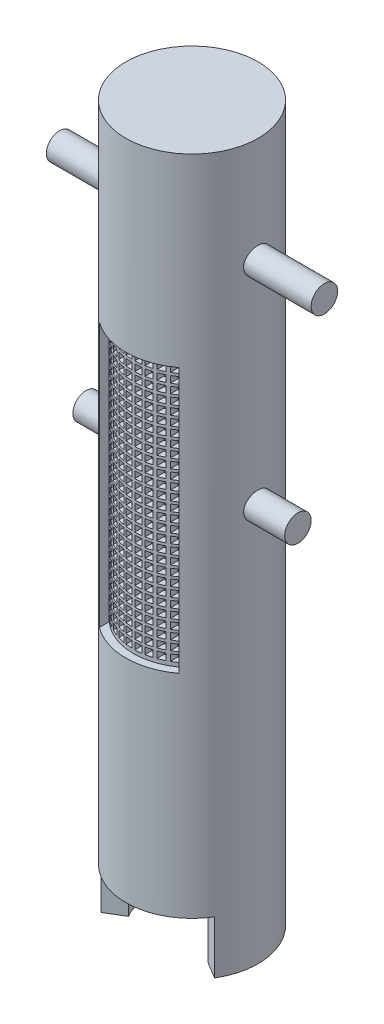
SolidWorks part; units mm, degrees
ref_plane "Front Plane" through (0, 0, 0) normal (0, 0, 1) x (1, 0, 0)
ref_plane "Top Plane" through (0, 0, 0) normal (0, 1, 0) x (1, 0, 0)
ref_plane "Right Plane" through (0, 0, 0) normal (1, 0, 0) x (0, 0, -1)
sketch "Sketch2" plane through (0, 0, 0) normal (0, 1, 0) x (1, 0, 0)
  circle A0 centre (0, 0) radius 5
  circle A1 centre (0, 0) radius 3.5
  dimension "D1" = 10
  dimension "D2" = 7
extrude "Boss-Extrude1" add sketch "Sketch2" along normal blind 40
sketch "Sketch3" plane through (0, 40, 0) normal (0, 1, 0) x (1, 0, 0)
  circle A0 centre (0, 0) radius 5
  circle A1 centre (0, 0) radius 1
  dimension "D1" = 10
  dimension "D2" = 2
sketch "Sketch4" plane through (0, 40, 0) normal (0, 1, 0) x (1, 0, 0)
  line L0 (3, 0) -> (3, -5)
  line L1 (3, 0) -> (-3, 0)
  line L3 (3, -5) -> (-3, -5)
  line L4 (-3, 0) -> (-3, -5)
  dimension "D1" = 6
  dimension "D2" = 5
  dimension "D3" = 3
  dimension "D4" = 5
  dimension "D5" = 3
extrude "Cut-Extrude1" cut sketch "Sketch4" against normal blind 20
extrude "Boss-Extrude2" add sketch "Sketch3" along normal blind 1
sketch "Sketch5" plane through (0, 41, 0) normal (0, 1, 0) x (1, 0, 0)
  circle A0 centre (0, 0) radius 5
  circle A1 centre (0, 0) radius 3.5
  dimension "D1" = 10
  dimension "D2" = 7
extrude "Boss-Extrude3" add sketch "Sketch5" along normal blind 10
sketch "Sketch6" plane through (0, 51, 0) normal (0, 1, 0) x (1, 0, 0)
  line L0 (2.5, 0) -> (2.5, 5)
  line L5 (2.5, 0) -> (-2.5, 0)
  line L7 (2.5, 5) -> (-2.5, 5)
  line L8 (-2.5, 0) -> (-2.5, 5)
  line L9 (-5.5, 0) -> (5.5, 0) construction
  line L10 (0, -5.5) -> (0, 5.5) construction
  dimension "D1" = 5
  dimension "D2" = 5
  dimension "D3" = 5
  dimension "D4" = 2.5
extrude "Cut-Extrude2" cut sketch "Sketch6" against normal blind 6
sketch "Sketch7" plane through (0, 51, 0) normal (0, 1, 0) x (1, 0, 0)
  circle A0 centre (0, 0) radius 5
  dimension "D1" = 10
extrude "Boss-Extrude4" add sketch "Sketch7" along normal blind 3
sketch "Sketch9" plane through (0, 20, 0) normal (0, 1, 0) x (1, 0, 0)
  line L0 (-3, -1.8028) -> (-3, -4) construction
  line L1 (3, -1.8028) -> (3, -4) construction
  line L2 (-3, -1.8028) -> (-3, -4) construction
  line L3 (3, -2.5286) -> (3, -3.2507)
  line L4 (-3, -2.5286) -> (-3, -3.2507)
  arc A0 (-3, -1.8028) -> (3, -1.8028) centre (0, 0) ccw construction
  arc A1 (-3, -2.9014) -> (3, -2.9014) centre (0, 0) ccw construction
  arc A2 (-3, -3.2507) -> (3.1797, -3.0752) centre (0, 0) ccw construction
  arc A3 (-3, -2.5286) -> (3, -2.5286) centre (0, 0) ccw
  arc A4 (-2.8203, -2.7276) -> (2.8203, -2.7276) centre (0, 0) ccw construction
  arc A5 (-3.1797, -3.0752) -> (3.1797, -3.0752) centre (0, 0) ccw construction
  arc A6 (-3, -3.2507) -> (3, -3.2507) centre (0, 0) ccw
  dimension "D1" = 0.25
  dimension "D2" = 0.25
extrude "Boss-Extrude5" add sketch "Sketch9" along normal up to surface (20 mm away) up to face at (0, 40, 1.8257)
ref_plane "Plane1" through (0, 0, 4.4235) normal (0, 0, 1) x (1, 0, 0)
sketch "Sketch10" plane through (0, 0, 4.4235) normal (0, 0, 1) x (1, 0, 0)
  line L0 (-3, 20) -> (3, 20) construction
  line L1 (3, 20) -> (3, 40) construction
  line L2 (3, 40) -> (-3, 40) construction
  line L3 (-3, 40) -> (-3, 20) construction
  line L4 (-2, 20.3) -> (-2, 20.8)
  line L5 (-2.7, 20.3) -> (-2.2, 20.3)
  line L6 (-2.7, 20.3) -> (-2.7, 20.8)
  line L7 (-2.7, 20.8) -> (-2.2, 20.8)
  line L8 (-2.2, 20.3) -> (-2.2, 20.8)
  line L9 (-2, 20.3) -> (-1.5, 20.3)
  line L10 (-1.5, 20.3) -> (-1.5, 20.8)
  line L11 (-2, 20.8) -> (-1.5, 20.8)
  line L12 (-1.3, 20.3) -> (-1.3, 20.8)
  line L13 (-1.3, 20.3) -> (-0.8, 20.3)
  line L14 (-0.8, 20.3) -> (-0.8, 20.8)
  line L15 (-1.3, 20.8) -> (-0.8, 20.8)
  line L16 (-0.6, 20.3) -> (-0.6, 20.8)
  line L17 (-0.6, 20.3) -> (-0.1, 20.3)
  line L18 (-0.1, 20.3) -> (-0.1, 20.8)
  line L19 (-0.6, 20.8) -> (-0.1, 20.8)
  line L20 (0.1, 20.3) -> (0.1, 20.8)
  line L21 (0.1, 20.3) -> (0.6, 20.3)
  line L22 (0.6, 20.3) -> (0.6, 20.8)
  line L23 (0.1, 20.8) -> (0.6, 20.8)
  line L24 (0.8, 20.3) -> (0.8, 20.8)
  line L25 (0.8, 20.3) -> (1.3, 20.3)
  line L26 (1.3, 20.3) -> (1.3, 20.8)
  line L27 (0.8, 20.8) -> (1.3, 20.8)
  line L28 (1.5, 20.3) -> (1.5, 20.8)
  line L29 (1.5, 20.3) -> (2, 20.3)
  line L30 (2, 20.3) -> (2, 20.8)
  line L31 (1.5, 20.8) -> (2, 20.8)
  line L32 (2.2, 20.3) -> (2.2, 20.8)
  line L33 (2.2, 20.3) -> (2.7, 20.3)
  line L34 (2.7, 20.3) -> (2.7, 20.8)
  line L35 (2.2, 20.8) -> (2.7, 20.8)
  line L36 (-2.7, 21) -> (-2.7, 21.5)
  line L37 (-2.7, 21) -> (-2.2, 21)
  line L38 (-2.2, 21) -> (-2.2, 21.5)
  line L39 (-2.7, 21.5) -> (-2.2, 21.5)
  line L40 (-2, 21) -> (-2, 21.5)
  line L41 (-2, 21.5) -> (-1.5, 21.5)
  line L42 (-1.5, 21) -> (-1.5, 21.5)
  line L43 (-2, 21) -> (-1.5, 21)
  line L44 (-1.3, 21) -> (-1.3, 21.5)
  line L45 (-1.3, 21.5) -> (-0.8, 21.5)
  line L46 (-0.8, 21) -> (-0.8, 21.5)
  line L47 (-1.3, 21) -> (-0.8, 21)
  line L48 (-0.6, 21) -> (-0.6, 21.5)
  line L49 (-0.6, 21.5) -> (-0.1, 21.5)
  line L50 (-0.1, 21) -> (-0.1, 21.5)
  line L51 (-0.6, 21) -> (-0.1, 21)
  line L52 (0.1, 21) -> (0.1, 21.5)
  line L53 (0.1, 21.5) -> (0.6, 21.5)
  line L54 (0.6, 21) -> (0.6, 21.5)
  line L55 (0.1, 21) -> (0.6, 21)
  line L56 (0.8, 21) -> (0.8, 21.5)
  line L57 (0.8, 21.5) -> (1.3, 21.5)
  line L58 (1.3, 21) -> (1.3, 21.5)
  line L59 (0.8, 21) -> (1.3, 21)
  line L60 (1.5, 21) -> (1.5, 21.5)
  line L61 (1.5, 21.5) -> (2, 21.5)
  line L62 (2, 21) -> (2, 21.5)
  line L63 (1.5, 21) -> (2, 21)
  line L64 (2.2, 21) -> (2.2, 21.5)
  line L65 (2.2, 21.5) -> (2.7, 21.5)
  line L66 (2.7, 21) -> (2.7, 21.5)
  line L67 (2.2, 21) -> (2.7, 21)
  line L68 (-2.7, 21.7) -> (-2.7, 22.2)
  line L69 (-2.7, 21.7) -> (-2.2, 21.7)
  line L70 (-2.2, 21.7) -> (-2.2, 22.2)
  line L71 (-2.7, 22.2) -> (-2.2, 22.2)
  line L72 (-2, 21.7) -> (-2, 22.2)
  line L73 (-2, 22.2) -> (-1.5, 22.2)
  line L74 (-1.5, 21.7) -> (-1.5, 22.2)
  line L75 (-2, 21.7) -> (-1.5, 21.7)
  line L76 (-1.3, 21.7) -> (-1.3, 22.2)
  line L77 (-1.3, 22.2) -> (-0.8, 22.2)
  line L78 (-0.8, 21.7) -> (-0.8, 22.2)
  line L79 (-1.3, 21.7) -> (-0.8, 21.7)
  line L80 (-0.6, 21.7) -> (-0.6, 22.2)
  line L81 (-0.6, 22.2) -> (-0.1, 22.2)
  line L82 (-0.1, 21.7) -> (-0.1, 22.2)
  line L83 (-0.6, 21.7) -> (-0.1, 21.7)
  line L84 (0.1, 21.7) -> (0.1, 22.2)
  line L85 (0.1, 22.2) -> (0.6, 22.2)
  line L86 (0.6, 21.7) -> (0.6, 22.2)
  line L87 (0.1, 21.7) -> (0.6, 21.7)
  line L88 (0.8, 21.7) -> (0.8, 22.2)
  line L89 (0.8, 22.2) -> (1.3, 22.2)
  line L90 (1.3, 21.7) -> (1.3, 22.2)
  line L91 (0.8, 21.7) -> (1.3, 21.7)
  line L92 (1.5, 21.7) -> (1.5, 22.2)
  line L93 (1.5, 22.2) -> (2, 22.2)
  line L94 (2, 21.7) -> (2, 22.2)
  line L95 (1.5, 21.7) -> (2, 21.7)
  line L96 (2.2, 21.7) -> (2.2, 22.2)
  line L97 (2.2, 22.2) -> (2.7, 22.2)
  line L98 (2.7, 21.7) -> (2.7, 22.2)
  line L99 (2.2, 21.7) -> (2.7, 21.7)
  line L100 (-2.7, 22.4) -> (-2.7, 22.9)
  line L101 (-2.7, 22.4) -> (-2.2, 22.4)
  line L102 (-2.2, 22.4) -> (-2.2, 22.9)
  line L103 (-2.7, 22.9) -> (-2.2, 22.9)
  line L104 (-2, 22.4) -> (-2, 22.9)
  line L105 (-2, 22.9) -> (-1.5, 22.9)
  line L106 (-1.5, 22.4) -> (-1.5, 22.9)
  line L107 (-2, 22.4) -> (-1.5, 22.4)
  line L108 (-1.3, 22.4) -> (-1.3, 22.9)
  line L109 (-1.3, 22.9) -> (-0.8, 22.9)
  line L110 (-0.8, 22.4) -> (-0.8, 22.9)
  line L111 (-1.3, 22.4) -> (-0.8, 22.4)
  line L112 (-0.6, 22.4) -> (-0.6, 22.9)
  line L113 (-0.6, 22.9) -> (-0.1, 22.9)
  line L114 (-0.1, 22.4) -> (-0.1, 22.9)
  line L115 (-0.6, 22.4) -> (-0.1, 22.4)
  line L116 (0.1, 22.4) -> (0.1, 22.9)
  line L117 (0.1, 22.9) -> (0.6, 22.9)
  line L118 (0.6, 22.4) -> (0.6, 22.9)
  line L119 (0.1, 22.4) -> (0.6, 22.4)
  line L120 (0.8, 22.4) -> (0.8, 22.9)
  line L121 (0.8, 22.9) -> (1.3, 22.9)
  line L122 (1.3, 22.4) -> (1.3, 22.9)
  line L123 (0.8, 22.4) -> (1.3, 22.4)
  line L124 (1.5, 22.4) -> (1.5, 22.9)
  line L125 (1.5, 22.9) -> (2, 22.9)
  line L126 (2, 22.4) -> (2, 22.9)
  line L127 (1.5, 22.4) -> (2, 22.4)
  line L128 (2.2, 22.4) -> (2.2, 22.9)
  line L129 (2.2, 22.9) -> (2.7, 22.9)
  line L130 (2.7, 22.4) -> (2.7, 22.9)
  line L131 (2.2, 22.4) -> (2.7, 22.4)
  line L132 (-2.7, 23.1) -> (-2.7, 23.6)
  line L133 (-2.7, 23.1) -> (-2.2, 23.1)
  line L134 (-2.2, 23.1) -> (-2.2, 23.6)
  line L135 (-2.7, 23.6) -> (-2.2, 23.6)
  line L136 (-2, 23.1) -> (-2, 23.6)
  line L137 (-2, 23.6) -> (-1.5, 23.6)
  line L138 (-1.5, 23.1) -> (-1.5, 23.6)
  line L139 (-2, 23.1) -> (-1.5, 23.1)
  line L140 (-1.3, 23.1) -> (-1.3, 23.6)
  line L141 (-1.3, 23.6) -> (-0.8, 23.6)
  line L142 (-0.8, 23.1) -> (-0.8, 23.6)
  line L143 (-1.3, 23.1) -> (-0.8, 23.1)
  line L144 (-0.6, 23.1) -> (-0.6, 23.6)
  line L145 (-0.6, 23.6) -> (-0.1, 23.6)
  line L146 (-0.1, 23.1) -> (-0.1, 23.6)
  line L147 (-0.6, 23.1) -> (-0.1, 23.1)
  line L148 (0.1, 23.1) -> (0.1, 23.6)
  line L149 (0.1, 23.6) -> (0.6, 23.6)
  line L150 (0.6, 23.1) -> (0.6, 23.6)
  line L151 (0.1, 23.1) -> (0.6, 23.1)
  line L152 (0.8, 23.1) -> (0.8, 23.6)
  line L153 (0.8, 23.6) -> (1.3, 23.6)
  line L154 (1.3, 23.1) -> (1.3, 23.6)
  line L155 (0.8, 23.1) -> (1.3, 23.1)
  line L156 (1.5, 23.1) -> (1.5, 23.6)
  line L157 (1.5, 23.6) -> (2, 23.6)
  line L158 (2, 23.1) -> (2, 23.6)
  line L159 (1.5, 23.1) -> (2, 23.1)
  line L160 (2.2, 23.1) -> (2.2, 23.6)
  line L161 (2.2, 23.6) -> (2.7, 23.6)
  line L162 (2.7, 23.1) -> (2.7, 23.6)
  line L163 (2.2, 23.1) -> (2.7, 23.1)
  line L164 (-2.7, 23.8) -> (-2.7, 24.3)
  line L165 (-2.7, 23.8) -> (-2.2, 23.8)
  line L166 (-2.2, 23.8) -> (-2.2, 24.3)
  line L167 (-2.7, 24.3) -> (-2.2, 24.3)
  line L168 (-2, 23.8) -> (-2, 24.3)
  line L169 (-2, 24.3) -> (-1.5, 24.3)
  line L170 (-1.5, 23.8) -> (-1.5, 24.3)
  line L171 (-2, 23.8) -> (-1.5, 23.8)
  line L172 (-1.3, 23.8) -> (-1.3, 24.3)
  line L173 (-1.3, 24.3) -> (-0.8, 24.3)
  line L174 (-0.8, 23.8) -> (-0.8, 24.3)
  line L175 (-1.3, 23.8) -> (-0.8, 23.8)
  line L176 (-0.6, 23.8) -> (-0.6, 24.3)
  line L177 (-0.6, 24.3) -> (-0.1, 24.3)
  line L178 (-0.1, 23.8) -> (-0.1, 24.3)
  line L179 (-0.6, 23.8) -> (-0.1, 23.8)
  line L180 (0.1, 23.8) -> (0.1, 24.3)
  line L181 (0.1, 24.3) -> (0.6, 24.3)
  line L182 (0.6, 23.8) -> (0.6, 24.3)
  line L183 (0.1, 23.8) -> (0.6, 23.8)
  line L184 (0.8, 23.8) -> (0.8, 24.3)
  line L185 (0.8, 24.3) -> (1.3, 24.3)
  line L186 (1.3, 23.8) -> (1.3, 24.3)
  line L187 (0.8, 23.8) -> (1.3, 23.8)
  line L188 (1.5, 23.8) -> (1.5, 24.3)
  line L189 (1.5, 24.3) -> (2, 24.3)
  line L190 (2, 23.8) -> (2, 24.3)
  line L191 (1.5, 23.8) -> (2, 23.8)
  line L192 (2.2, 23.8) -> (2.2, 24.3)
  line L193 (2.2, 24.3) -> (2.7, 24.3)
  line L194 (2.7, 23.8) -> (2.7, 24.3)
  line L195 (2.2, 23.8) -> (2.7, 23.8)
  line L196 (-2.7, 24.5) -> (-2.7, 25)
  line L197 (-2.7, 24.5) -> (-2.2, 24.5)
  line L198 (-2.2, 24.5) -> (-2.2, 25)
  line L199 (-2.7, 25) -> (-2.2, 25)
  line L200 (-2, 24.5) -> (-2, 25)
  line L201 (-2, 25) -> (-1.5, 25)
  line L202 (-1.5, 24.5) -> (-1.5, 25)
  line L203 (-2, 24.5) -> (-1.5, 24.5)
  line L204 (-1.3, 24.5) -> (-1.3, 25)
  line L205 (-1.3, 25) -> (-0.8, 25)
  line L206 (-0.8, 24.5) -> (-0.8, 25)
  line L207 (-1.3, 24.5) -> (-0.8, 24.5)
  line L208 (-0.6, 24.5) -> (-0.6, 25)
  line L209 (-0.6, 25) -> (-0.1, 25)
  line L210 (-0.1, 24.5) -> (-0.1, 25)
  line L211 (-0.6, 24.5) -> (-0.1, 24.5)
  line L212 (0.1, 24.5) -> (0.1, 25)
  line L213 (0.1, 25) -> (0.6, 25)
  line L214 (0.6, 24.5) -> (0.6, 25)
  line L215 (0.1, 24.5) -> (0.6, 24.5)
  line L216 (0.8, 24.5) -> (0.8, 25)
  line L217 (0.8, 25) -> (1.3, 25)
  line L218 (1.3, 24.5) -> (1.3, 25)
  line L219 (0.8, 24.5) -> (1.3, 24.5)
  line L220 (1.5, 24.5) -> (1.5, 25)
  line L221 (1.5, 25) -> (2, 25)
  line L222 (2, 24.5) -> (2, 25)
  line L223 (1.5, 24.5) -> (2, 24.5)
  line L224 (2.2, 24.5) -> (2.2, 25)
  line L225 (2.2, 25) -> (2.7, 25)
  line L226 (2.7, 24.5) -> (2.7, 25)
  line L227 (2.2, 24.5) -> (2.7, 24.5)
  line L228 (-2.7, 25.2) -> (-2.7, 25.7)
  line L229 (-2.7, 25.2) -> (-2.2, 25.2)
  line L230 (-2.2, 25.2) -> (-2.2, 25.7)
  line L231 (-2.7, 25.7) -> (-2.2, 25.7)
  line L232 (-2, 25.2) -> (-2, 25.7)
  line L233 (-2, 25.7) -> (-1.5, 25.7)
  line L234 (-1.5, 25.2) -> (-1.5, 25.7)
  line L235 (-2, 25.2) -> (-1.5, 25.2)
  line L236 (-1.3, 25.2) -> (-1.3, 25.7)
  line L237 (-1.3, 25.7) -> (-0.8, 25.7)
  line L238 (-0.8, 25.2) -> (-0.8, 25.7)
  line L239 (-1.3, 25.2) -> (-0.8, 25.2)
  line L240 (-0.6, 25.2) -> (-0.6, 25.7)
  line L241 (-0.6, 25.7) -> (-0.1, 25.7)
  line L242 (-0.1, 25.2) -> (-0.1, 25.7)
  line L243 (-0.6, 25.2) -> (-0.1, 25.2)
  line L244 (0.1, 25.2) -> (0.1, 25.7)
  line L245 (0.1, 25.7) -> (0.6, 25.7)
  line L246 (0.6, 25.2) -> (0.6, 25.7)
  line L247 (0.1, 25.2) -> (0.6, 25.2)
  line L248 (0.8, 25.2) -> (0.8, 25.7)
  line L249 (0.8, 25.7) -> (1.3, 25.7)
  line L250 (1.3, 25.2) -> (1.3, 25.7)
  line L251 (0.8, 25.2) -> (1.3, 25.2)
  line L252 (1.5, 25.2) -> (1.5, 25.7)
  line L253 (1.5, 25.7) -> (2, 25.7)
  line L254 (2, 25.2) -> (2, 25.7)
  line L255 (1.5, 25.2) -> (2, 25.2)
  line L256 (2.2, 25.2) -> (2.2, 25.7)
  line L257 (2.2, 25.7) -> (2.7, 25.7)
  line L258 (2.7, 25.2) -> (2.7, 25.7)
  line L259 (2.2, 25.2) -> (2.7, 25.2)
  line L260 (-2.7, 25.9) -> (-2.7, 26.4)
  line L261 (-2.7, 25.9) -> (-2.2, 25.9)
  line L262 (-2.2, 25.9) -> (-2.2, 26.4)
  line L263 (-2.7, 26.4) -> (-2.2, 26.4)
  line L264 (-2, 25.9) -> (-2, 26.4)
  line L265 (-2, 26.4) -> (-1.5, 26.4)
  line L266 (-1.5, 25.9) -> (-1.5, 26.4)
  line L267 (-2, 25.9) -> (-1.5, 25.9)
  line L268 (-1.3, 25.9) -> (-1.3, 26.4)
  line L269 (-1.3, 26.4) -> (-0.8, 26.4)
  line L270 (-0.8, 25.9) -> (-0.8, 26.4)
  line L271 (-1.3, 25.9) -> (-0.8, 25.9)
  line L272 (-0.6, 25.9) -> (-0.6, 26.4)
  line L273 (-0.6, 26.4) -> (-0.1, 26.4)
  line L274 (-0.1, 25.9) -> (-0.1, 26.4)
  line L275 (-0.6, 25.9) -> (-0.1, 25.9)
  line L276 (0.1, 25.9) -> (0.1, 26.4)
  line L277 (0.1, 26.4) -> (0.6, 26.4)
  line L278 (0.6, 25.9) -> (0.6, 26.4)
  line L279 (0.1, 25.9) -> (0.6, 25.9)
  line L280 (0.8, 25.9) -> (0.8, 26.4)
  line L281 (0.8, 26.4) -> (1.3, 26.4)
  line L282 (1.3, 25.9) -> (1.3, 26.4)
  line L283 (0.8, 25.9) -> (1.3, 25.9)
  line L284 (1.5, 25.9) -> (1.5, 26.4)
  line L285 (1.5, 26.4) -> (2, 26.4)
  line L286 (2, 25.9) -> (2, 26.4)
  line L287 (1.5, 25.9) -> (2, 25.9)
  line L288 (2.2, 25.9) -> (2.2, 26.4)
  line L289 (2.2, 26.4) -> (2.7, 26.4)
  line L290 (2.7, 25.9) -> (2.7, 26.4)
  line L291 (2.2, 25.9) -> (2.7, 25.9)
  line L292 (-2.7, 26.5999) -> (-2.7, 27.0999)
  line L293 (-2.7, 26.5999) -> (-2.2, 26.5999)
  line L294 (-2.2, 26.5999) -> (-2.2, 27.0999)
  line L295 (-2.7, 27.0999) -> (-2.2, 27.0999)
  line L296 (-2, 26.5999) -> (-2, 27.0999)
  line L297 (-2, 27.0999) -> (-1.5, 27.0999)
  line L298 (-1.5, 26.5999) -> (-1.5, 27.0999)
  line L299 (-2, 26.5999) -> (-1.5, 26.5999)
  line L300 (-1.3, 26.5999) -> (-1.3, 27.0999)
  line L301 (-1.3, 27.0999) -> (-0.8, 27.0999)
  line L302 (-0.8, 26.5999) -> (-0.8, 27.0999)
  line L303 (-1.3, 26.5999) -> (-0.8, 26.5999)
  line L304 (-0.6, 26.5999) -> (-0.6, 27.0999)
  line L305 (-0.6, 27.0999) -> (-0.1, 27.0999)
  line L306 (-0.1, 26.5999) -> (-0.1, 27.0999)
  line L307 (-0.6, 26.5999) -> (-0.1, 26.5999)
  line L308 (0.1, 26.5999) -> (0.1, 27.0999)
  line L309 (0.1, 27.0999) -> (0.6, 27.0999)
  line L310 (0.6, 26.5999) -> (0.6, 27.0999)
  line L311 (0.1, 26.5999) -> (0.6, 26.5999)
  line L312 (0.8, 26.5999) -> (0.8, 27.0999)
  line L313 (0.8, 27.0999) -> (1.3, 27.0999)
  line L314 (1.3, 26.5999) -> (1.3, 27.0999)
  line L315 (0.8, 26.5999) -> (1.3, 26.5999)
  line L316 (1.5, 26.5999) -> (1.5, 27.0999)
  line L317 (1.5, 27.0999) -> (2, 27.0999)
  line L318 (2, 26.5999) -> (2, 27.0999)
  line L319 (1.5, 26.5999) -> (2, 26.5999)
  line L320 (2.2, 26.5999) -> (2.2, 27.0999)
  line L321 (2.2, 27.0999) -> (2.7, 27.0999)
  line L322 (2.7, 26.5999) -> (2.7, 27.0999)
  line L323 (2.2, 26.5999) -> (2.7, 26.5999)
  line L324 (-2.7, 27.2999) -> (-2.7, 27.7999)
  line L325 (-2.7, 27.2999) -> (-2.2, 27.2999)
  line L326 (-2.2, 27.2999) -> (-2.2, 27.7999)
  line L327 (-2.7, 27.7999) -> (-2.2, 27.7999)
  line L328 (-2, 27.2999) -> (-2, 27.7999)
  line L329 (-2, 27.7999) -> (-1.5, 27.7999)
  line L330 (-1.5, 27.2999) -> (-1.5, 27.7999)
  line L331 (-2, 27.2999) -> (-1.5, 27.2999)
  line L332 (-1.3, 27.2999) -> (-1.3, 27.7999)
  line L333 (-1.3, 27.7999) -> (-0.8, 27.7999)
  line L334 (-0.8, 27.2999) -> (-0.8, 27.7999)
  line L335 (-1.3, 27.2999) -> (-0.8, 27.2999)
  line L336 (-0.6, 27.2999) -> (-0.6, 27.7999)
  line L337 (-0.6, 27.7999) -> (-0.1, 27.7999)
  line L338 (-0.1, 27.2999) -> (-0.1, 27.7999)
  line L339 (-0.6, 27.2999) -> (-0.1, 27.2999)
  line L340 (0.1, 27.2999) -> (0.1, 27.7999)
  line L341 (0.1, 27.7999) -> (0.6, 27.7999)
  line L342 (0.6, 27.2999) -> (0.6, 27.7999)
  line L343 (0.1, 27.2999) -> (0.6, 27.2999)
  line L344 (0.8, 27.2999) -> (0.8, 27.7999)
  line L345 (0.8, 27.7999) -> (1.3, 27.7999)
  line L346 (1.3, 27.2999) -> (1.3, 27.7999)
  line L347 (0.8, 27.2999) -> (1.3, 27.2999)
  line L348 (1.5, 27.2999) -> (1.5, 27.7999)
  line L349 (1.5, 27.7999) -> (2, 27.7999)
  line L350 (2, 27.2999) -> (2, 27.7999)
  line L351 (1.5, 27.2999) -> (2, 27.2999)
  line L352 (2.2, 27.2999) -> (2.2, 27.7999)
  line L353 (2.2, 27.7999) -> (2.7, 27.7999)
  line L354 (2.7, 27.2999) -> (2.7, 27.7999)
  line L355 (2.2, 27.2999) -> (2.7, 27.2999)
  line L356 (-2.7, 27.9999) -> (-2.7, 28.4999)
  line L357 (-2.7, 27.9999) -> (-2.2, 27.9999)
  line L358 (-2.2, 27.9999) -> (-2.2, 28.4999)
  line L359 (-2.7, 28.4999) -> (-2.2, 28.4999)
  line L360 (-2, 27.9999) -> (-2, 28.4999)
  line L361 (-2, 28.4999) -> (-1.5, 28.4999)
  line L362 (-1.5, 27.9999) -> (-1.5, 28.4999)
  line L363 (-2, 27.9999) -> (-1.5, 27.9999)
  line L364 (-1.3, 27.9999) -> (-1.3, 28.4999)
  line L365 (-1.3, 28.4999) -> (-0.8, 28.4999)
  line L366 (-0.8, 27.9999) -> (-0.8, 28.4999)
  line L367 (-1.3, 27.9999) -> (-0.8, 27.9999)
  line L368 (-0.6, 27.9999) -> (-0.6, 28.4999)
  line L369 (-0.6, 28.4999) -> (-0.1, 28.4999)
  line L370 (-0.1, 27.9999) -> (-0.1, 28.4999)
  line L371 (-0.6, 27.9999) -> (-0.1, 27.9999)
  line L372 (0.1, 27.9999) -> (0.1, 28.4999)
  line L373 (0.1, 28.4999) -> (0.6, 28.4999)
  line L374 (0.6, 27.9999) -> (0.6, 28.4999)
  line L375 (0.1, 27.9999) -> (0.6, 27.9999)
  line L376 (0.8, 27.9999) -> (0.8, 28.4999)
  line L377 (0.8, 28.4999) -> (1.3, 28.4999)
  line L378 (1.3, 27.9999) -> (1.3, 28.4999)
  line L379 (0.8, 27.9999) -> (1.3, 27.9999)
  line L380 (1.5, 27.9999) -> (1.5, 28.4999)
  line L381 (1.5, 28.4999) -> (2, 28.4999)
  line L382 (2, 27.9999) -> (2, 28.4999)
  line L383 (1.5, 27.9999) -> (2, 27.9999)
  line L384 (2.2, 27.9999) -> (2.2, 28.4999)
  line L385 (2.2, 28.4999) -> (2.7, 28.4999)
  line L386 (2.7, 27.9999) -> (2.7, 28.4999)
  line L387 (2.2, 27.9999) -> (2.7, 27.9999)
  line L388 (-2.7, 28.6999) -> (-2.7, 29.1999)
  line L389 (-2.7, 28.6999) -> (-2.2, 28.6999)
  line L390 (-2.2, 28.6999) -> (-2.2, 29.1999)
  line L391 (-2.7, 29.1999) -> (-2.2, 29.1999)
  line L392 (-2, 28.6999) -> (-2, 29.1999)
  line L393 (-2, 29.1999) -> (-1.5, 29.1999)
  line L394 (-1.5, 28.6999) -> (-1.5, 29.1999)
  line L395 (-2, 28.6999) -> (-1.5, 28.6999)
  line L396 (-1.3, 28.6999) -> (-1.3, 29.1999)
  line L397 (-1.3, 29.1999) -> (-0.8, 29.1999)
  line L398 (-0.8, 28.6999) -> (-0.8, 29.1999)
  line L399 (-1.3, 28.6999) -> (-0.8, 28.6999)
  line L400 (-0.6, 28.6999) -> (-0.6, 29.1999)
  line L401 (-0.6, 29.1999) -> (-0.1, 29.1999)
  line L402 (-0.1, 28.6999) -> (-0.1, 29.1999)
  line L403 (-0.6, 28.6999) -> (-0.1, 28.6999)
  line L404 (0.1, 28.6999) -> (0.1, 29.1999)
  line L405 (0.1, 29.1999) -> (0.6, 29.1999)
  line L406 (0.6, 28.6999) -> (0.6, 29.1999)
  line L407 (0.1, 28.6999) -> (0.6, 28.6999)
  line L408 (0.8, 28.6999) -> (0.8, 29.1999)
  line L409 (0.8, 29.1999) -> (1.3, 29.1999)
  line L410 (1.3, 28.6999) -> (1.3, 29.1999)
  line L411 (0.8, 28.6999) -> (1.3, 28.6999)
  line L412 (1.5, 28.6999) -> (1.5, 29.1999)
  line L413 (1.5, 29.1999) -> (2, 29.1999)
  line L414 (2, 28.6999) -> (2, 29.1999)
  line L415 (1.5, 28.6999) -> (2, 28.6999)
  line L416 (2.2, 28.6999) -> (2.2, 29.1999)
  line L417 (2.2, 29.1999) -> (2.7, 29.1999)
  line L418 (2.7, 28.6999) -> (2.7, 29.1999)
  line L419 (2.2, 28.6999) -> (2.7, 28.6999)
  line L420 (-2.7, 29.3999) -> (-2.7, 29.8999)
  line L421 (-2.7, 29.3999) -> (-2.2, 29.3999)
  line L422 (-2.2, 29.3999) -> (-2.2, 29.8999)
  line L423 (-2.7, 29.8999) -> (-2.2, 29.8999)
  line L424 (-2, 29.3999) -> (-2, 29.8999)
  line L425 (-2, 29.8999) -> (-1.5, 29.8999)
  line L426 (-1.5, 29.3999) -> (-1.5, 29.8999)
  line L427 (-2, 29.3999) -> (-1.5, 29.3999)
  line L428 (-1.3, 29.3999) -> (-1.3, 29.8999)
  line L429 (-1.3, 29.8999) -> (-0.8, 29.8999)
  line L430 (-0.8, 29.3999) -> (-0.8, 29.8999)
  line L431 (-1.3, 29.3999) -> (-0.8, 29.3999)
  line L432 (-0.6, 29.3999) -> (-0.6, 29.8999)
  line L433 (-0.6, 29.8999) -> (-0.1, 29.8999)
  line L434 (-0.1, 29.3999) -> (-0.1, 29.8999)
  line L435 (-0.6, 29.3999) -> (-0.1, 29.3999)
  line L436 (0.1, 29.3999) -> (0.1, 29.8999)
  line L437 (0.1, 29.8999) -> (0.6, 29.8999)
  line L438 (0.6, 29.3999) -> (0.6, 29.8999)
  line L439 (0.1, 29.3999) -> (0.6, 29.3999)
  line L440 (0.8, 29.3999) -> (0.8, 29.8999)
  line L441 (0.8, 29.8999) -> (1.3, 29.8999)
  line L442 (1.3, 29.3999) -> (1.3, 29.8999)
  line L443 (0.8, 29.3999) -> (1.3, 29.3999)
  line L444 (1.5, 29.3999) -> (1.5, 29.8999)
  line L445 (1.5, 29.8999) -> (2, 29.8999)
  line L446 (2, 29.3999) -> (2, 29.8999)
  line L447 (1.5, 29.3999) -> (2, 29.3999)
  line L448 (2.2, 29.3999) -> (2.2, 29.8999)
  line L449 (2.2, 29.8999) -> (2.7, 29.8999)
  line L450 (2.7, 29.3999) -> (2.7, 29.8999)
  line L451 (2.2, 29.3999) -> (2.7, 29.3999)
  line L452 (-2.7, 30.0999) -> (-2.7, 30.5999)
  line L453 (-2.7, 30.0999) -> (-2.2, 30.0999)
  line L454 (-2.2, 30.0999) -> (-2.2, 30.5999)
  line L455 (-2.7, 30.5999) -> (-2.2, 30.5999)
  line L456 (-2, 30.0999) -> (-2, 30.5999)
  line L457 (-2, 30.5999) -> (-1.5, 30.5999)
  line L458 (-1.5, 30.0999) -> (-1.5, 30.5999)
  line L459 (-2, 30.0999) -> (-1.5, 30.0999)
  line L460 (-1.3, 30.0999) -> (-1.3, 30.5999)
  line L461 (-1.3, 30.5999) -> (-0.8, 30.5999)
  line L462 (-0.8, 30.0999) -> (-0.8, 30.5999)
  line L463 (-1.3, 30.0999) -> (-0.8, 30.0999)
  line L464 (-0.6, 30.0999) -> (-0.6, 30.5999)
  line L465 (-0.6, 30.5999) -> (-0.1, 30.5999)
  line L466 (-0.1, 30.0999) -> (-0.1, 30.5999)
  line L467 (-0.6, 30.0999) -> (-0.1, 30.0999)
  line L468 (0.1, 30.0999) -> (0.1, 30.5999)
  line L469 (0.1, 30.5999) -> (0.6, 30.5999)
  line L470 (0.6, 30.0999) -> (0.6, 30.5999)
  line L471 (0.1, 30.0999) -> (0.6, 30.0999)
  line L472 (0.8, 30.0999) -> (0.8, 30.5999)
  line L473 (0.8, 30.5999) -> (1.3, 30.5999)
  line L474 (1.3, 30.0999) -> (1.3, 30.5999)
  line L475 (0.8, 30.0999) -> (1.3, 30.0999)
  line L476 (1.5, 30.0999) -> (1.5, 30.5999)
  line L477 (1.5, 30.5999) -> (2, 30.5999)
  line L478 (2, 30.0999) -> (2, 30.5999)
  line L479 (1.5, 30.0999) -> (2, 30.0999)
  line L480 (2.2, 30.0999) -> (2.2, 30.5999)
  line L481 (2.2, 30.5999) -> (2.7, 30.5999)
  line L482 (2.7, 30.0999) -> (2.7, 30.5999)
  line L483 (2.2, 30.0999) -> (2.7, 30.0999)
  line L484 (-2.7, 30.7999) -> (-2.7, 31.2999)
  line L485 (-2.7, 30.7999) -> (-2.2, 30.7999)
  line L486 (-2.2, 30.7999) -> (-2.2, 31.2999)
  line L487 (-2.7, 31.2999) -> (-2.2, 31.2999)
  line L488 (-2, 30.7999) -> (-2, 31.2999)
  line L489 (-2, 31.2999) -> (-1.5, 31.2999)
  line L490 (-1.5, 30.7999) -> (-1.5, 31.2999)
  line L491 (-2, 30.7999) -> (-1.5, 30.7999)
  line L492 (-1.3, 30.7999) -> (-1.3, 31.2999)
  line L493 (-1.3, 31.2999) -> (-0.8, 31.2999)
  line L494 (-0.8, 30.7999) -> (-0.8, 31.2999)
  line L495 (-1.3, 30.7999) -> (-0.8, 30.7999)
  line L496 (-0.6, 30.7999) -> (-0.6, 31.2999)
  line L497 (-0.6, 31.2999) -> (-0.1, 31.2999)
  line L498 (-0.1, 30.7999) -> (-0.1, 31.2999)
  line L499 (-0.6, 30.7999) -> (-0.1, 30.7999)
  line L500 (0.1, 30.7999) -> (0.1, 31.2999)
  line L501 (0.1, 31.2999) -> (0.6, 31.2999)
  line L502 (0.6, 30.7999) -> (0.6, 31.2999)
  line L503 (0.1, 30.7999) -> (0.6, 30.7999)
  line L504 (0.8, 30.7999) -> (0.8, 31.2999)
  line L505 (0.8, 31.2999) -> (1.3, 31.2999)
  line L506 (1.3, 30.7999) -> (1.3, 31.2999)
  line L507 (0.8, 30.7999) -> (1.3, 30.7999)
  line L508 (1.5, 30.7999) -> (1.5, 31.2999)
  line L509 (1.5, 31.2999) -> (2, 31.2999)
  line L510 (2, 30.7999) -> (2, 31.2999)
  line L511 (1.5, 30.7999) -> (2, 30.7999)
  line L512 (2.2, 30.7999) -> (2.2, 31.2999)
  line L513 (2.2, 31.2999) -> (2.7, 31.2999)
  line L514 (2.7, 30.7999) -> (2.7, 31.2999)
  line L515 (2.2, 30.7999) -> (2.7, 30.7999)
  line L516 (-2.7, 31.4999) -> (-2.7, 31.9999)
  line L517 (-2.7, 31.4999) -> (-2.2, 31.4999)
  line L518 (-2.2, 31.4999) -> (-2.2, 31.9999)
  line L519 (-2.7, 31.9999) -> (-2.2, 31.9999)
  line L520 (-2, 31.4999) -> (-2, 31.9999)
  line L521 (-2, 31.9999) -> (-1.5, 31.9999)
  line L522 (-1.5, 31.4999) -> (-1.5, 31.9999)
  line L523 (-2, 31.4999) -> (-1.5, 31.4999)
  line L524 (-1.3, 31.4999) -> (-1.3, 31.9999)
  line L525 (-1.3, 31.9999) -> (-0.8, 31.9999)
  line L526 (-0.8, 31.4999) -> (-0.8, 31.9999)
  line L527 (-1.3, 31.4999) -> (-0.8, 31.4999)
  line L528 (-0.6, 31.4999) -> (-0.6, 31.9999)
  line L529 (-0.6, 31.9999) -> (-0.1, 31.9999)
  line L530 (-0.1, 31.4999) -> (-0.1, 31.9999)
  line L531 (-0.6, 31.4999) -> (-0.1, 31.4999)
  line L532 (0.1, 31.4999) -> (0.1, 31.9999)
  line L533 (0.1, 31.9999) -> (0.6, 31.9999)
  line L534 (0.6, 31.4999) -> (0.6, 31.9999)
  line L535 (0.1, 31.4999) -> (0.6, 31.4999)
  line L536 (0.8, 31.4999) -> (0.8, 31.9999)
  line L537 (0.8, 31.9999) -> (1.3, 31.9999)
  line L538 (1.3, 31.4999) -> (1.3, 31.9999)
  line L539 (0.8, 31.4999) -> (1.3, 31.4999)
  line L540 (1.5, 31.4999) -> (1.5, 31.9999)
  line L541 (1.5, 31.9999) -> (2, 31.9999)
  line L542 (2, 31.4999) -> (2, 31.9999)
  line L543 (1.5, 31.4999) -> (2, 31.4999)
  line L544 (2.2, 31.4999) -> (2.2, 31.9999)
  line L545 (2.2, 31.9999) -> (2.7, 31.9999)
  line L546 (2.7, 31.4999) -> (2.7, 31.9999)
  line L547 (2.2, 31.4999) -> (2.7, 31.4999)
  line L548 (-2.7, 32.1999) -> (-2.7, 32.6999)
  line L549 (-2.7, 32.1999) -> (-2.2, 32.1999)
  line L550 (-2.2, 32.1999) -> (-2.2, 32.6999)
  line L551 (-2.7, 32.6999) -> (-2.2, 32.6999)
  line L552 (-2, 32.1999) -> (-2, 32.6999)
  line L553 (-2, 32.6999) -> (-1.5, 32.6999)
  line L554 (-1.5, 32.1999) -> (-1.5, 32.6999)
  line L555 (-2, 32.1999) -> (-1.5, 32.1999)
  line L556 (-1.3, 32.1999) -> (-1.3, 32.6999)
  line L557 (-1.3, 32.6999) -> (-0.8, 32.6999)
  line L558 (-0.8, 32.1999) -> (-0.8, 32.6999)
  line L559 (-1.3, 32.1999) -> (-0.8, 32.1999)
  line L560 (-0.6, 32.1999) -> (-0.6, 32.6999)
  line L561 (-0.6, 32.6999) -> (-0.1, 32.6999)
  line L562 (-0.1, 32.1999) -> (-0.1, 32.6999)
  line L563 (-0.6, 32.1999) -> (-0.1, 32.1999)
  line L564 (0.1, 32.1999) -> (0.1, 32.6999)
  line L565 (0.1, 32.6999) -> (0.6, 32.6999)
  line L566 (0.6, 32.1999) -> (0.6, 32.6999)
  line L567 (0.1, 32.1999) -> (0.6, 32.1999)
  line L568 (0.8, 32.1999) -> (0.8, 32.6999)
  line L569 (0.8, 32.6999) -> (1.3, 32.6999)
  line L570 (1.3, 32.1999) -> (1.3, 32.6999)
  line L571 (0.8, 32.1999) -> (1.3, 32.1999)
  line L572 (1.5, 32.1999) -> (1.5, 32.6999)
  line L573 (1.5, 32.6999) -> (2, 32.6999)
  line L574 (2, 32.1999) -> (2, 32.6999)
  line L575 (1.5, 32.1999) -> (2, 32.1999)
  line L576 (2.2, 32.1999) -> (2.2, 32.6999)
  line L577 (2.2, 32.6999) -> (2.7, 32.6999)
  line L578 (2.7, 32.1999) -> (2.7, 32.6999)
  line L579 (2.2, 32.1999) -> (2.7, 32.1999)
  line L580 (-2.7, 32.8999) -> (-2.7, 33.3999)
  line L581 (-2.7, 32.8999) -> (-2.2, 32.8999)
  line L582 (-2.2, 32.8999) -> (-2.2, 33.3999)
  line L583 (-2.7, 33.3999) -> (-2.2, 33.3999)
  line L584 (-2, 32.8999) -> (-2, 33.3999)
  line L585 (-2, 33.3999) -> (-1.5, 33.3999)
  line L586 (-1.5, 32.8999) -> (-1.5, 33.3999)
  line L587 (-2, 32.8999) -> (-1.5, 32.8999)
  line L588 (-1.3, 32.8999) -> (-1.3, 33.3999)
  line L589 (-1.3, 33.3999) -> (-0.8, 33.3999)
  line L590 (-0.8, 32.8999) -> (-0.8, 33.3999)
  line L591 (-1.3, 32.8999) -> (-0.8, 32.8999)
  line L592 (-0.6, 32.8999) -> (-0.6, 33.3999)
  line L593 (-0.6, 33.3999) -> (-0.1, 33.3999)
  line L594 (-0.1, 32.8999) -> (-0.1, 33.3999)
  line L595 (-0.6, 32.8999) -> (-0.1, 32.8999)
  line L596 (0.1, 32.8999) -> (0.1, 33.3999)
  line L597 (0.1, 33.3999) -> (0.6, 33.3999)
  line L598 (0.6, 32.8999) -> (0.6, 33.3999)
  line L599 (0.1, 32.8999) -> (0.6, 32.8999)
  line L600 (0.8, 32.8999) -> (0.8, 33.3999)
  line L601 (0.8, 33.3999) -> (1.3, 33.3999)
  line L602 (1.3, 32.8999) -> (1.3, 33.3999)
  line L603 (0.8, 32.8999) -> (1.3, 32.8999)
  line L604 (1.5, 32.8999) -> (1.5, 33.3999)
  line L605 (1.5, 33.3999) -> (2, 33.3999)
  line L606 (2, 32.8999) -> (2, 33.3999)
  line L607 (1.5, 32.8999) -> (2, 32.8999)
  line L608 (2.2, 32.8999) -> (2.2, 33.3999)
  line L609 (2.2, 33.3999) -> (2.7, 33.3999)
  line L610 (2.7, 32.8999) -> (2.7, 33.3999)
  line L611 (2.2, 32.8999) -> (2.7, 32.8999)
  line L612 (-2.7, 33.5999) -> (-2.7, 34.0999)
  line L613 (-2.7, 33.5999) -> (-2.2, 33.5999)
  line L614 (-2.2, 33.5999) -> (-2.2, 34.0999)
  line L615 (-2.7, 34.0999) -> (-2.2, 34.0999)
  line L616 (-2, 33.5999) -> (-2, 34.0999)
  line L617 (-2, 34.0999) -> (-1.5, 34.0999)
  line L618 (-1.5, 33.5999) -> (-1.5, 34.0999)
  line L619 (-2, 33.5999) -> (-1.5, 33.5999)
  line L620 (-1.3, 33.5999) -> (-1.3, 34.0999)
  line L621 (-1.3, 34.0999) -> (-0.8, 34.0999)
  line L622 (-0.8, 33.5999) -> (-0.8, 34.0999)
  line L623 (-1.3, 33.5999) -> (-0.8, 33.5999)
  line L624 (-0.6, 33.5999) -> (-0.6, 34.0999)
  line L625 (-0.6, 34.0999) -> (-0.1, 34.0999)
  line L626 (-0.1, 33.5999) -> (-0.1, 34.0999)
  line L627 (-0.6, 33.5999) -> (-0.1, 33.5999)
  line L628 (0.1, 33.5999) -> (0.1, 34.0999)
  line L629 (0.1, 34.0999) -> (0.6, 34.0999)
  line L630 (0.6, 33.5999) -> (0.6, 34.0999)
  line L631 (0.1, 33.5999) -> (0.6, 33.5999)
  line L632 (0.8, 33.5999) -> (0.8, 34.0999)
  line L633 (0.8, 34.0999) -> (1.3, 34.0999)
  line L634 (1.3, 33.5999) -> (1.3, 34.0999)
  line L635 (0.8, 33.5999) -> (1.3, 33.5999)
  line L636 (1.5, 33.5999) -> (1.5, 34.0999)
  line L637 (1.5, 34.0999) -> (2, 34.0999)
  line L638 (2, 33.5999) -> (2, 34.0999)
  line L639 (1.5, 33.5999) -> (2, 33.5999)
  line L640 (2.2, 33.5999) -> (2.2, 34.0999)
  line L641 (2.2, 34.0999) -> (2.7, 34.0999)
  line L642 (2.7, 33.5999) -> (2.7, 34.0999)
  line L643 (2.2, 33.5999) -> (2.7, 33.5999)
  line L644 (-2.7, 34.2999) -> (-2.7, 34.7999)
  line L645 (-2.7, 34.2999) -> (-2.2, 34.2999)
  line L646 (-2.2, 34.2999) -> (-2.2, 34.7999)
  line L647 (-2.7, 34.7999) -> (-2.2, 34.7999)
  line L648 (-2, 34.2999) -> (-2, 34.7999)
  line L649 (-2, 34.7999) -> (-1.5, 34.7999)
  line L650 (-1.5, 34.2999) -> (-1.5, 34.7999)
  line L651 (-2, 34.2999) -> (-1.5, 34.2999)
  line L652 (-1.3, 34.2999) -> (-1.3, 34.7999)
  line L653 (-1.3, 34.7999) -> (-0.8, 34.7999)
  line L654 (-0.8, 34.2999) -> (-0.8, 34.7999)
  line L655 (-1.3, 34.2999) -> (-0.8, 34.2999)
  line L656 (-0.6, 34.2999) -> (-0.6, 34.7999)
  line L657 (-0.6, 34.7999) -> (-0.1, 34.7999)
  line L658 (-0.1, 34.2999) -> (-0.1, 34.7999)
  line L659 (-0.6, 34.2999) -> (-0.1, 34.2999)
  line L660 (0.1, 34.2999) -> (0.1, 34.7999)
  line L661 (0.1, 34.7999) -> (0.6, 34.7999)
  line L662 (0.6, 34.2999) -> (0.6, 34.7999)
  line L663 (0.1, 34.2999) -> (0.6, 34.2999)
  line L664 (0.8, 34.2999) -> (0.8, 34.7999)
  line L665 (0.8, 34.7999) -> (1.3, 34.7999)
  line L666 (1.3, 34.2999) -> (1.3, 34.7999)
  line L667 (0.8, 34.2999) -> (1.3, 34.2999)
  line L668 (1.5, 34.2999) -> (1.5, 34.7999)
  line L669 (1.5, 34.7999) -> (2, 34.7999)
  line L670 (2, 34.2999) -> (2, 34.7999)
  line L671 (1.5, 34.2999) -> (2, 34.2999)
  line L672 (2.2, 34.2999) -> (2.2, 34.7999)
  line L673 (2.2, 34.7999) -> (2.7, 34.7999)
  line L674 (2.7, 34.2999) -> (2.7, 34.7999)
  line L675 (2.2, 34.2999) -> (2.7, 34.2999)
  line L676 (-2.7, 34.9999) -> (-2.7, 35.4999)
  line L677 (-2.7, 34.9999) -> (-2.2, 34.9999)
  line L678 (-2.2, 34.9999) -> (-2.2, 35.4999)
  line L679 (-2.7, 35.4999) -> (-2.2, 35.4999)
  line L680 (-2, 34.9999) -> (-2, 35.4999)
  line L681 (-2, 35.4999) -> (-1.5, 35.4999)
  line L682 (-1.5, 34.9999) -> (-1.5, 35.4999)
  line L683 (-2, 34.9999) -> (-1.5, 34.9999)
  line L684 (-1.3, 34.9999) -> (-1.3, 35.4999)
  line L685 (-1.3, 35.4999) -> (-0.8, 35.4999)
  line L686 (-0.8, 34.9999) -> (-0.8, 35.4999)
  line L687 (-1.3, 34.9999) -> (-0.8, 34.9999)
  line L688 (-0.6, 34.9999) -> (-0.6, 35.4999)
  line L689 (-0.6, 35.4999) -> (-0.1, 35.4999)
  line L690 (-0.1, 34.9999) -> (-0.1, 35.4999)
  line L691 (-0.6, 34.9999) -> (-0.1, 34.9999)
  line L692 (0.1, 34.9999) -> (0.1, 35.4999)
  line L693 (0.1, 35.4999) -> (0.6, 35.4999)
  line L694 (0.6, 34.9999) -> (0.6, 35.4999)
  line L695 (0.1, 34.9999) -> (0.6, 34.9999)
  line L696 (0.8, 34.9999) -> (0.8, 35.4999)
  line L697 (0.8, 35.4999) -> (1.3, 35.4999)
  line L698 (1.3, 34.9999) -> (1.3, 35.4999)
  line L699 (0.8, 34.9999) -> (1.3, 34.9999)
  line L700 (1.5, 34.9999) -> (1.5, 35.4999)
  line L701 (1.5, 35.4999) -> (2, 35.4999)
  line L702 (2, 34.9999) -> (2, 35.4999)
  line L703 (1.5, 34.9999) -> (2, 34.9999)
  line L704 (2.2, 34.9999) -> (2.2, 35.4999)
  line L705 (2.2, 35.4999) -> (2.7, 35.4999)
  line L706 (2.7, 34.9999) -> (2.7, 35.4999)
  line L707 (2.2, 34.9999) -> (2.7, 34.9999)
  line L708 (-2.7, 35.6999) -> (-2.7, 36.1999)
  line L709 (-2.7, 35.6999) -> (-2.2, 35.6999)
  line L710 (-2.2, 35.6999) -> (-2.2, 36.1999)
  line L711 (-2.7, 36.1999) -> (-2.2, 36.1999)
  line L712 (-2, 35.6999) -> (-2, 36.1999)
  line L713 (-2, 36.1999) -> (-1.5, 36.1999)
  line L714 (-1.5, 35.6999) -> (-1.5, 36.1999)
  line L715 (-2, 35.6999) -> (-1.5, 35.6999)
  line L716 (-1.3, 35.6999) -> (-1.3, 36.1999)
  line L717 (-1.3, 36.1999) -> (-0.8, 36.1999)
  line L718 (-0.8, 35.6999) -> (-0.8, 36.1999)
  line L719 (-1.3, 35.6999) -> (-0.8, 35.6999)
  line L720 (-0.6, 35.6999) -> (-0.6, 36.1999)
  line L721 (-0.6, 36.1999) -> (-0.1, 36.1999)
  line L722 (-0.1, 35.6999) -> (-0.1, 36.1999)
  line L723 (-0.6, 35.6999) -> (-0.1, 35.6999)
  line L724 (0.1, 35.6999) -> (0.1, 36.1999)
  line L725 (0.1, 36.1999) -> (0.6, 36.1999)
  line L726 (0.6, 35.6999) -> (0.6, 36.1999)
  line L727 (0.1, 35.6999) -> (0.6, 35.6999)
  line L728 (0.8, 35.6999) -> (0.8, 36.1999)
  line L729 (0.8, 36.1999) -> (1.3, 36.1999)
  line L730 (1.3, 35.6999) -> (1.3, 36.1999)
  line L731 (0.8, 35.6999) -> (1.3, 35.6999)
  line L732 (1.5, 35.6999) -> (1.5, 36.1999)
  line L733 (1.5, 36.1999) -> (2, 36.1999)
  line L734 (2, 35.6999) -> (2, 36.1999)
  line L735 (1.5, 35.6999) -> (2, 35.6999)
  line L736 (2.2, 35.6999) -> (2.2, 36.1999)
  line L737 (2.2, 36.1999) -> (2.7, 36.1999)
  line L738 (2.7, 35.6999) -> (2.7, 36.1999)
  line L739 (2.2, 35.6999) -> (2.7, 35.6999)
  line L740 (-2.7, 36.3999) -> (-2.7, 36.8999)
  line L741 (-2.7, 36.3999) -> (-2.2, 36.3999)
  line L742 (-2.2, 36.3999) -> (-2.2, 36.8999)
  line L743 (-2.7, 36.8999) -> (-2.2, 36.8999)
  line L744 (-2, 36.3999) -> (-2, 36.8999)
  line L745 (-2, 36.8999) -> (-1.5, 36.8999)
  line L746 (-1.5, 36.3999) -> (-1.5, 36.8999)
  line L747 (-2, 36.3999) -> (-1.5, 36.3999)
  line L748 (-1.3, 36.3999) -> (-1.3, 36.8999)
  line L749 (-1.3, 36.8999) -> (-0.8, 36.8999)
  line L750 (-0.8, 36.3999) -> (-0.8, 36.8999)
  line L751 (-1.3, 36.3999) -> (-0.8, 36.3999)
  line L752 (-0.6, 36.3999) -> (-0.6, 36.8999)
  line L753 (-0.6, 36.8999) -> (-0.1, 36.8999)
  line L754 (-0.1, 36.3999) -> (-0.1, 36.8999)
  line L755 (-0.6, 36.3999) -> (-0.1, 36.3999)
  line L756 (0.1, 36.3999) -> (0.1, 36.8999)
  line L757 (0.1, 36.8999) -> (0.6, 36.8999)
  line L758 (0.6, 36.3999) -> (0.6, 36.8999)
  line L759 (0.1, 36.3999) -> (0.6, 36.3999)
  line L760 (0.8, 36.3999) -> (0.8, 36.8999)
  line L761 (0.8, 36.8999) -> (1.3, 36.8999)
  line L762 (1.3, 36.3999) -> (1.3, 36.8999)
  line L763 (0.8, 36.3999) -> (1.3, 36.3999)
  line L764 (1.5, 36.3999) -> (1.5, 36.8999)
  line L765 (1.5, 36.8999) -> (2, 36.8999)
  line L766 (2, 36.3999) -> (2, 36.8999)
  line L767 (1.5, 36.3999) -> (2, 36.3999)
  line L768 (2.2, 36.3999) -> (2.2, 36.8999)
  line L769 (2.2, 36.8999) -> (2.7, 36.8999)
  line L770 (2.7, 36.3999) -> (2.7, 36.8999)
  line L771 (2.2, 36.3999) -> (2.7, 36.3999)
  line L772 (-2.7, 37.0999) -> (-2.7, 37.5999)
  line L773 (-2.7, 37.0999) -> (-2.2, 37.0999)
  line L774 (-2.2, 37.0999) -> (-2.2, 37.5999)
  line L775 (-2.7, 37.5999) -> (-2.2, 37.5999)
  line L776 (-2, 37.0999) -> (-2, 37.5999)
  line L777 (-2, 37.5999) -> (-1.5, 37.5999)
  line L778 (-1.5, 37.0999) -> (-1.5, 37.5999)
  line L779 (-2, 37.0999) -> (-1.5, 37.0999)
  line L780 (-1.3, 37.0999) -> (-1.3, 37.5999)
  line L781 (-1.3, 37.5999) -> (-0.8, 37.5999)
  line L782 (-0.8, 37.0999) -> (-0.8, 37.5999)
  line L783 (-1.3, 37.0999) -> (-0.8, 37.0999)
  line L784 (-0.6, 37.0999) -> (-0.6, 37.5999)
  line L785 (-0.6, 37.5999) -> (-0.1, 37.5999)
  line L786 (-0.1, 37.0999) -> (-0.1, 37.5999)
  line L787 (-0.6, 37.0999) -> (-0.1, 37.0999)
  line L788 (0.1, 37.0999) -> (0.1, 37.5999)
  line L789 (0.1, 37.5999) -> (0.6, 37.5999)
  line L790 (0.6, 37.0999) -> (0.6, 37.5999)
  line L791 (0.1, 37.0999) -> (0.6, 37.0999)
  line L792 (0.8, 37.0999) -> (0.8, 37.5999)
  line L793 (0.8, 37.5999) -> (1.3, 37.5999)
  line L794 (1.3, 37.0999) -> (1.3, 37.5999)
  line L795 (0.8, 37.0999) -> (1.3, 37.0999)
  line L796 (1.5, 37.0999) -> (1.5, 37.5999)
  line L797 (1.5, 37.5999) -> (2, 37.5999)
  line L798 (2, 37.0999) -> (2, 37.5999)
  line L799 (1.5, 37.0999) -> (2, 37.0999)
  line L800 (2.2, 37.0999) -> (2.2, 37.5999)
  line L801 (2.2, 37.5999) -> (2.7, 37.5999)
  line L802 (2.7, 37.0999) -> (2.7, 37.5999)
  line L803 (2.2, 37.0999) -> (2.7, 37.0999)
  line L804 (-2.7, 37.7999) -> (-2.7, 38.2999)
  line L805 (-2.7, 37.7999) -> (-2.2, 37.7999)
  line L806 (-2.2, 37.7999) -> (-2.2, 38.2999)
  line L807 (-2.7, 38.2999) -> (-2.2, 38.2999)
  line L808 (-2, 37.7999) -> (-2, 38.2999)
  line L809 (-2, 38.2999) -> (-1.5, 38.2999)
  line L810 (-1.5, 37.7999) -> (-1.5, 38.2999)
  line L811 (-2, 37.7999) -> (-1.5, 37.7999)
  line L812 (-1.3, 37.7999) -> (-1.3, 38.2999)
  line L813 (-1.3, 38.2999) -> (-0.8, 38.2999)
  line L814 (-0.8, 37.7999) -> (-0.8, 38.2999)
  line L815 (-1.3, 37.7999) -> (-0.8, 37.7999)
  line L816 (-0.6, 37.7999) -> (-0.6, 38.2999)
  line L817 (-0.6, 38.2999) -> (-0.1, 38.2999)
  line L818 (-0.1, 37.7999) -> (-0.1, 38.2999)
  line L819 (-0.6, 37.7999) -> (-0.1, 37.7999)
  line L820 (0.1, 37.7999) -> (0.1, 38.2999)
  line L821 (0.1, 38.2999) -> (0.6, 38.2999)
  line L822 (0.6, 37.7999) -> (0.6, 38.2999)
  line L823 (0.1, 37.7999) -> (0.6, 37.7999)
  line L824 (0.8, 37.7999) -> (0.8, 38.2999)
  line L825 (0.8, 38.2999) -> (1.3, 38.2999)
  line L826 (1.3, 37.7999) -> (1.3, 38.2999)
  line L827 (0.8, 37.7999) -> (1.3, 37.7999)
  line L828 (1.5, 37.7999) -> (1.5, 38.2999)
  line L829 (1.5, 38.2999) -> (2, 38.2999)
  line L830 (2, 37.7999) -> (2, 38.2999)
  line L831 (1.5, 37.7999) -> (2, 37.7999)
  line L832 (2.2, 37.7999) -> (2.2, 38.2999)
  line L833 (2.2, 38.2999) -> (2.7, 38.2999)
  line L834 (2.7, 37.7999) -> (2.7, 38.2999)
  line L835 (2.2, 37.7999) -> (2.7, 37.7999)
  line L836 (-2.7, 38.4998) -> (-2.7, 38.9998)
  line L837 (-2.7, 38.4998) -> (-2.2, 38.4998)
  line L838 (-2.2, 38.4998) -> (-2.2, 38.9998)
  line L839 (-2.7, 38.9998) -> (-2.2, 38.9998)
  line L840 (-2, 38.4998) -> (-2, 38.9998)
  line L841 (-2, 38.9998) -> (-1.5, 38.9998)
  line L842 (-1.5, 38.4998) -> (-1.5, 38.9998)
  line L843 (-2, 38.4998) -> (-1.5, 38.4998)
  line L844 (-1.3, 38.4998) -> (-1.3, 38.9998)
  line L845 (-1.3, 38.9998) -> (-0.8, 38.9998)
  line L846 (-0.8, 38.4998) -> (-0.8, 38.9998)
  line L847 (-1.3, 38.4998) -> (-0.8, 38.4998)
  line L848 (-0.6, 38.4998) -> (-0.6, 38.9998)
  line L849 (-0.6, 38.9998) -> (-0.1, 38.9998)
  line L850 (-0.1, 38.4998) -> (-0.1, 38.9998)
  line L851 (-0.6, 38.4998) -> (-0.1, 38.4998)
  line L852 (0.1, 38.4998) -> (0.1, 38.9998)
  line L853 (0.1, 38.9998) -> (0.6, 38.9998)
  line L854 (0.6, 38.4998) -> (0.6, 38.9998)
  line L855 (0.1, 38.4998) -> (0.6, 38.4998)
  line L856 (0.8, 38.4998) -> (0.8, 38.9998)
  line L857 (0.8, 38.9998) -> (1.3, 38.9998)
  line L858 (1.3, 38.4998) -> (1.3, 38.9998)
  line L859 (0.8, 38.4998) -> (1.3, 38.4998)
  line L860 (1.5, 38.4998) -> (1.5, 38.9998)
  line L861 (1.5, 38.9998) -> (2, 38.9998)
  line L862 (2, 38.4998) -> (2, 38.9998)
  line L863 (1.5, 38.4998) -> (2, 38.4998)
  line L864 (2.2, 38.4998) -> (2.2, 38.9998)
  line L865 (2.2, 38.9998) -> (2.7, 38.9998)
  line L866 (2.7, 38.4998) -> (2.7, 38.9998)
  line L867 (2.2, 38.4998) -> (2.7, 38.4998)
  line L868 (-2.7, 39.1998) -> (-2.7, 39.6998)
  line L869 (-2.7, 39.1998) -> (-2.2, 39.1998)
  line L870 (-2.2, 39.1998) -> (-2.2, 39.6998)
  line L871 (-2.7, 39.6998) -> (-2.2, 39.6998)
  line L872 (-2, 39.1998) -> (-2, 39.6998)
  line L873 (-2, 39.6998) -> (-1.5, 39.6998)
  line L874 (-1.5, 39.1998) -> (-1.5, 39.6998)
  line L875 (-2, 39.1998) -> (-1.5, 39.1998)
  line L876 (-1.3, 39.1998) -> (-1.3, 39.6998)
  line L877 (-1.3, 39.6998) -> (-0.8, 39.6998)
  line L878 (-0.8, 39.1998) -> (-0.8, 39.6998)
  line L879 (-1.3, 39.1998) -> (-0.8, 39.1998)
  line L880 (-0.6, 39.1998) -> (-0.6, 39.6998)
  line L881 (-0.6, 39.6998) -> (-0.1, 39.6998)
  line L882 (-0.1, 39.1998) -> (-0.1, 39.6998)
  line L883 (-0.6, 39.1998) -> (-0.1, 39.1998)
  line L884 (0.1, 39.1998) -> (0.1, 39.6998)
  line L885 (0.1, 39.6998) -> (0.6, 39.6998)
  line L886 (0.6, 39.1998) -> (0.6, 39.6998)
  line L887 (0.1, 39.1998) -> (0.6, 39.1998)
  line L888 (0.8, 39.1998) -> (0.8, 39.6998)
  line L889 (0.8, 39.6998) -> (1.3, 39.6998)
  line L890 (1.3, 39.1998) -> (1.3, 39.6998)
  line L891 (0.8, 39.1998) -> (1.3, 39.1998)
  line L892 (1.5, 39.1998) -> (1.5, 39.6998)
  line L893 (1.5, 39.6998) -> (2, 39.6998)
  line L894 (2, 39.1998) -> (2, 39.6998)
  line L895 (1.5, 39.1998) -> (2, 39.1998)
  line L896 (2.2, 39.1998) -> (2.2, 39.6998)
  line L897 (2.2, 39.6998) -> (2.7, 39.6998)
  line L898 (2.7, 39.1998) -> (2.7, 39.6998)
  line L899 (2.2, 39.1998) -> (2.7, 39.1998)
  dimension "D1" = 0.5
  dimension "D2" = 0.5
  dimension "D3" = 0.3
  dimension "D4" = 0.3
  dimension "D5" = 8
  dimension "D6" = 0.3
  dimension "D8" = 0.3002
  dimension "D7" = 28
extrude "Cut-Extrude3" cut sketch "Sketch10" against normal up to surface (1.5768 mm away) up to face at (0, 30, 3.226)
ref_plane "Plane2" through (-5, 0, 0) normal (-1, 0, 0) x (0, 0, 1)
sketch "Sketch11" plane through (-5, 0, 0) normal (-1, 0, 0) x (0, 0, 1)
  line L0 (-5, 0) -> (5, 0) construction
  line L1 (-5, 45) -> (-5, 0) construction
  circle A0 centre (0, 30) radius 1
  dimension "D2" = 2
  dimension "D1" = 30
  dimension "D3" = 5
extrude "B: length 2" add sketch "Sketch11" along normal blind 3 separate body
extrude "B: to shell 2" add sketch "Sketch11<2>" against normal up to surface (0.101 mm away) up to face at (0, 48, -4.6651)
sketch "Sketch11<2>" plane through (-5, 0, 0) normal (-1, 0, 0) x (0, 0, 1) same geometry as "Sketch11"
ref_plane "Plane3" through (5, 0, 0) normal (1, 0, 0) x (0, 0, -1)
sketch "Sketch12" plane through (5, 0, 0) normal (1, 0, 0) x (0, 0, -1)
  line L0 (-5, 0) -> (5, 0) construction
  line L1 (-5, 54) -> (-5, 40) construction
  circle A0 centre (0, 30) radius 1
  dimension "D2" = 2
  dimension "D1" = 30
  dimension "D3" = 5
extrude "B: to shell" add sketch "Sketch12" against normal up to surface (0.101 mm away) up to face at (0, 54, 5)
extrude "B: length" add sketch "Sketch12<2>" along normal blind 3
sketch "Sketch12<2>" plane through (5, 0, 0) normal (1, 0, 0) x (0, 0, -1) same geometry as "Sketch12"
sketch "Sketch13" plane through (-5, 0, 0) normal (-1, 0, 0) x (0, 0, 1)
  line L0 (5, 54) -> (-5, 54) construction
  line L1 (-5, 45) -> (-5, 0) construction
  circle A0 centre (0, 46) radius 1
  dimension "D1" = 2
  dimension "D2" = 8
  dimension "D3" = 5
extrude "T: length" add sketch "Sketch13" along normal blind 5 separate body
extrude "T: to shell" add sketch "Sketch13<2>" against normal up to surface (0.101 mm away) up to face at (4.9034, 29.7921, 0.9782)
sketch "Sketch13<2>" plane through (-5, 0, 0) normal (-1, 0, 0) x (0, 0, 1) same geometry as "Sketch13"
sketch "Sketch14" plane through (5, 0, 0) normal (1, 0, 0) x (0, 0, -1)
  line L0 (5, 54) -> (-5, 54) construction
  line L1 (5, 0) -> (5, 45) construction
  circle A0 centre (0, 46) radius 1
  dimension "D1" = 2
  dimension "D2" = 8
  dimension "D3" = 5
extrude "T: to shell 2" add sketch "Sketch14" against normal up to surface (0.101 mm away) up to face at (-4.9034, 29.7921, -0.9782)
extrude "T: length 2" add sketch "Sketch14<2>" along normal blind 5
sketch "Sketch14<2>" plane through (5, 0, 0) normal (1, 0, 0) x (0, 0, -1) same geometry as "Sketch14"
ref_plane "Plane5" through (0, 0, 5) normal (0, 0, 1) x (1, 0, 0)
sketch "Sketch16" plane through (0, 0, 5) normal (0, 0, 1) x (1, 0, 0)
  line L0 (-5, 0) -> (5, 0) construction
  line L1 (-3, 4) -> (3, 4)
  line L2 (-3, 4) -> (-3, 0)
  line L3 (-3, 0) -> (3, 0)
  line L4 (3, 4) -> (3, 0)
  line L5 (-3, 4) -> (3, 0) construction
  line L6 (-3, 0) -> (3, 4) construction
  point P0 (0, 2)
  dimension "D1" = 6
  dimension "D2" = 4
extrude "Cut-Extrude4" cut sketch "Sketch16" against normal up to next
sketch "Sketch17" plane through (0, 0, 0) normal (0, -1, 0) x (1, 0, 0)
  line L0 (-3, 1.8028) -> (-3, 4)
  line L1 (-4.2857, 2.5754) -> (-3, 1.8028)
  line L2 (-4.2857, 2.5754) -> (0, 0) construction
  line L3 (0, -5.5) -> (0, 5.5) construction
  line L4 (3, 1.8028) -> (3, 4)
  line L5 (4.2857, 2.5754) -> (3, 1.8028)
  arc A0 (-4.2857, 2.5754) -> (-3, 4) centre (0, 0) cw
  arc A1 (-3, 4) -> (3, 4) centre (0, 0) ccw construction
  arc A2 (4.2857, 2.5754) -> (3, 4) centre (0, 0) ccw
extrude "Cut-Extrude5" cut sketch "Sketch17" against normal up to surface (4 mm away) up to face at (0, 4, 3.5757)
ref_plane "Plane6" through (0, 0, 4.5) normal (0, 0, 1) x (1, 0, 0)
sketch "Sketch18" plane through (0, 0, 4.5) normal (0, 0, 1) x (1, 0, 0)
  line L0 (5, 54) -> (-5, 54) construction
  circle A0 centre (0, 44.5) radius 0.75
  dimension "D1" = 1.5
  dimension "D2" = 9.5
extrude "Boss-Extrude6" add sketch "Sketch18" against normal blind 3
sketch "Sketch19" plane through (0, 51, 0) normal (0, -1, 0) x (1, 0, 0)
  circle A0 centre (0, 0) radius 0.75
  dimension "D1" = 1.5
extrude "Boss-Extrude7" add sketch "Sketch19" along normal blind 5
sketch "Sketch20" plane through (0, 51, 0) normal (0, -1, 0) x (1, 0, 0)
  circle A1 centre (0, 0) radius 2
  circle A2 centre (0, 0) radius 0.75
  dimension "D1" = 1.5
  dimension "D2" = 4
extrude "Cut-Extrude6" cut sketch "Sketch20" against normal blind 1.5
